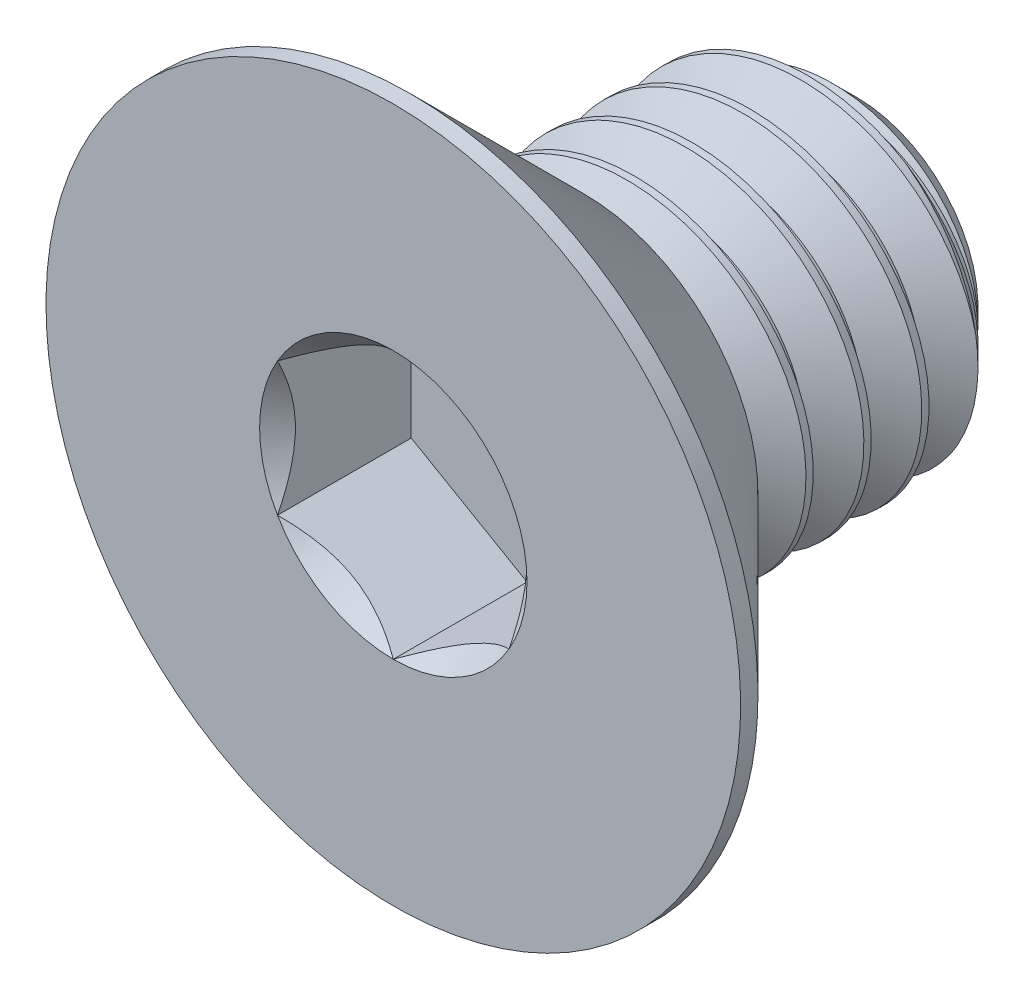
SolidWorks part; units mm, degrees
ref_plane "Front" through (0, 0, 0) normal (0, 0, 1) x (1, 0, 0)
ref_plane "Top" through (0, 0, 0) normal (0, 1, 0) x (1, 0, 0)
ref_plane "Right" through (0, 0, 0) normal (1, 0, 0) x (0, 0, -1)
sketch "Sketch1" plane through (0, 0, 0) normal (1, 0, 0) x (0, 0, -1)
  line L0 (-4, 6) -> (-3.7, 6) construction
  line L1 (-3.7, 6) -> (-0.7, 3) construction
  line L2 (-4, 3) -> (4, 3) construction
  line L3 (4, 3) -> (4, 0) construction
  line L4 (4, 0) -> (-4, 0) construction
  line L5 (-4, 0) -> (-4, 6) construction
  line L6 (-4, 6) -> (-4, -6) construction
  line L7 (4, 3) -> (4, -3) construction
  line L8 (-4, -6) -> (-3.7, -6) construction
  line L9 (-3.7, -6) -> (-0.7, -3) construction
  line L11 (-4, 3) -> (-4, 0) construction
  line L12 (-0.7, 3) -> (-0.7, 0) construction
  line L13 (3.9375, 3.1083) -> (4.4375, 2.2422) construction
  line L14 (4.4375, 2.2422) -> (4.9375, 3.1083) construction
  line L15 (4.9375, 3.1083) -> (3.9375, 3.1083) construction
  line L16 (4.4375, 3.1083) -> (4.4375, 3) construction
  line L17 (4.4375, 3) -> (4.4375, 2.3505) construction
  line L18 (4.4375, 2.3505) -> (4.4375, 2.2422) construction
  line L19 (4.4375, 3.0541) -> (4.9063, 3.0541) construction
  line L20 (4.4375, 3.0541) -> (3.9688, 3.0541) construction
  line L21 (4, 3) -> (4.875, 3) construction
  line L22 (4.375, 2.3505) -> (4.5, 2.3505) construction
  line L23 (4, -3) -> (-0.7, -3) construction
  point P10 (1.5, -3)
  point P24 (-0.7, 3)
  point P30 (0, 0)
  dimension "Head Diameter" = 12
  dimension "Head Height" = 3.3
  dimension "Length" = 8
  dimension "Countersink Angle" = 90
  dimension "Thread Pitch" = 1
  dimension "D2" = 0.125
  dimension "Thread Size" = 6
  dimension "D1" = 2.5
sketch "Sketch2" plane through (0, 0, 0) normal (0, 0, 1) x (1, 0, 0)
  line L1 (0, 2.3094) -> (-2, 1.1547) construction
  line L2 (-2, 1.1547) -> (-2, -1.1547) construction
  line L3 (-2, -1.1547) -> (0, -2.3094) construction
  line L4 (0, -2.3094) -> (2, -1.1547) construction
  line L5 (2, -1.1547) -> (2, 1.1547) construction
  line L6 (2, 1.1547) -> (0, 2.3094) construction
  circle A0 centre (0, 0) radius 2 construction
  dimension "Drive Size" = 4
sketch "Sketch3" plane through (0, 0, 0) normal (1, 0, 0) x (0, 0, -1)
  line L0 (-4, 3) -> (4, 3)
  line L1 (4, 3) -> (4, 0)
  line L2 (4, 0) -> (-4, 0)
  line L3 (-4, 0) -> (-4, 3)
revolve "Revolve1" add sketch "Sketch3" angle 360 about L4
chamfer "Chamfer1" distance 0.9 angle 45 1 edges at (0, 3, -4)
sketch "Sketch6" plane through (0, 0, 0) normal (1, 0, 0) x (0, 0, -1)
  line L0 (-4, 6) -> (-3.7, 6)
  line L1 (-3.7, 6) -> (-0.7, 3)
  line L2 (-0.7, 3) -> (-0.7, 0)
  line L3 (-0.7, 0) -> (-4, 0)
  line L4 (-4, 0) -> (-4, 6)
revolve "Revolve2" add sketch "Sketch6" angle 360 about L4
sketch "Sketch8" plane through (0, 0, 4) normal (0, 0, 1) x (1, 0, 0)
  line L0 (0, 2.3094) -> (-2, 1.1547) construction
  line L1 (2, 1.1547) -> (0, 2.3094) construction
  line L2 (2, -1.1547) -> (2, 1.1547) construction
  line L3 (0, -2.3094) -> (2, -1.1547) construction
  line L4 (-2, 1.1547) -> (-2, -1.1547) construction
  line L5 (-2, -1.1547) -> (0, -2.3094) construction
  line L6 (0, 2.3094) -> (-2, 1.1547)
  line L7 (2, 1.1547) -> (0, 2.3094)
  line L8 (2, -1.1547) -> (2, 1.1547)
  line L9 (0, -2.3094) -> (2, -1.1547)
  line L10 (-2, 1.1547) -> (-2, -1.1547)
  line L11 (-2, -1.1547) -> (0, -2.3094)
extrude "Cut-Extrude1" cut sketch "Sketch8" against normal blind 2.31
sketch "Sketch9" plane through (0, 0, 4) normal (0, 0, 1) x (1, 0, 0)
  circle A0 centre (0, 0) radius 2.3094
extrude "Cut-Extrude2" cut sketch "Sketch9" against normal up to next (2.31 mm away) draft 45
ref_plane "Plane1" through (0, 0, 0.7) normal (0, 0, 1) x (1, 0, 0)
split "Split1" trim tools "Plane1" bodies to split 124 resulting bodies 126 127
sketch "Sketch4" plane through (0, 0, -4) normal (0, 0, -1) x (-1, 0, 0)
  circle A0 centre (0, 0) radius 3 construction
  circle A1 centre (0, 0) radius 3
curve "Helix/Spiral1" pitch 1 height 8 radius 3 centre (0, 0, -4) axis (0, 0, 1) start towards (0, 1, 0)
sketch "Sketch10" plane through (0, 0, 0) normal (1, 0, 0) x (0, 0, -1)
  line L0 (3.9688, 3.0541) -> (4.9063, 3.0541)
  line L1 (4.9063, 3.0541) -> (4.5, 2.3505)
  line L2 (4.5, 2.3505) -> (4.375, 2.3505)
  line L3 (4.375, 2.3505) -> (3.9688, 3.0541)
sweep "Cut-Sweep1" cut profiles "Sketch10" path "Helix/Spiral1" align with end faces yes
combine bodies "Combine1" operation type add bodies to combine 130 126
sketch "Sketch11" plane through (0, 0, 4) normal (0, 0, 1) x (1, 0, 0)
  circle A0 centre (0, 0) radius 1.25
  point P3 (0, 0)
  dimension "D1" = 2.5
extrude "Cut-Extrude3" cut sketch "Sketch11" along normal offset from surface (4.19 mm away) 1.5 from surface up to face at (0, 0, 1.69) starting at face at (0, 2.1, -4)
thread "Thread3" pitch 0.6 method cut profile "Thread Profile3" start angle 0, offset 0, length 10, pitch 0.6, diameter 2.5
ref_plane "Plane4" through (-1.25, 0, 0.19) normal (0, -1, 0) x (-1, 0, 0)
sketch "Thread Profile3" plane through (-1.25, 0, 0.19) normal (0, -1, 0) x (-1, 0, 0)
  line L0 (0, 0) -> (0, 0.6) construction
  line L1 (0, 0) -> (0.3248, 0.1875)
  line L2 (0.3248, 0.1875) -> (0.3248, 0.2625)
  line L3 (0.3248, 0.2625) -> (0, 0.45)
  line L4 (0.3248, 0.225) -> (0, 0.225) construction
  line L11 (0, 0) -> (0, 0.45)
  point P2 (0, 0)
  dimension "Pitch" = 0.6
  dimension "Profile_Angle" = 60
  dimension "Profile_Land" = 0.075
  dimension "Profile_Height" = 0.3248
equation "\"D2@Sketch1\" = \"Thread Pitch@Sketch1\" / 8"
equation "\"D4@Helix/Spiral1\"=\"Thread Pitch@Sketch1\""
equation "\"D1@Chamfer1\"=\"Thread Size@Sketch1\"*.15"
equation "\"D1@Cut-Extrude1\"=\"Head Height@Sketch1\"*.7"
equation "\"D1@Sketch1\"=\"Thread Pitch@Sketch1\"*2.5"
equation "\"D3@Helix/Spiral1\"=\"Length@Sketch1\""
